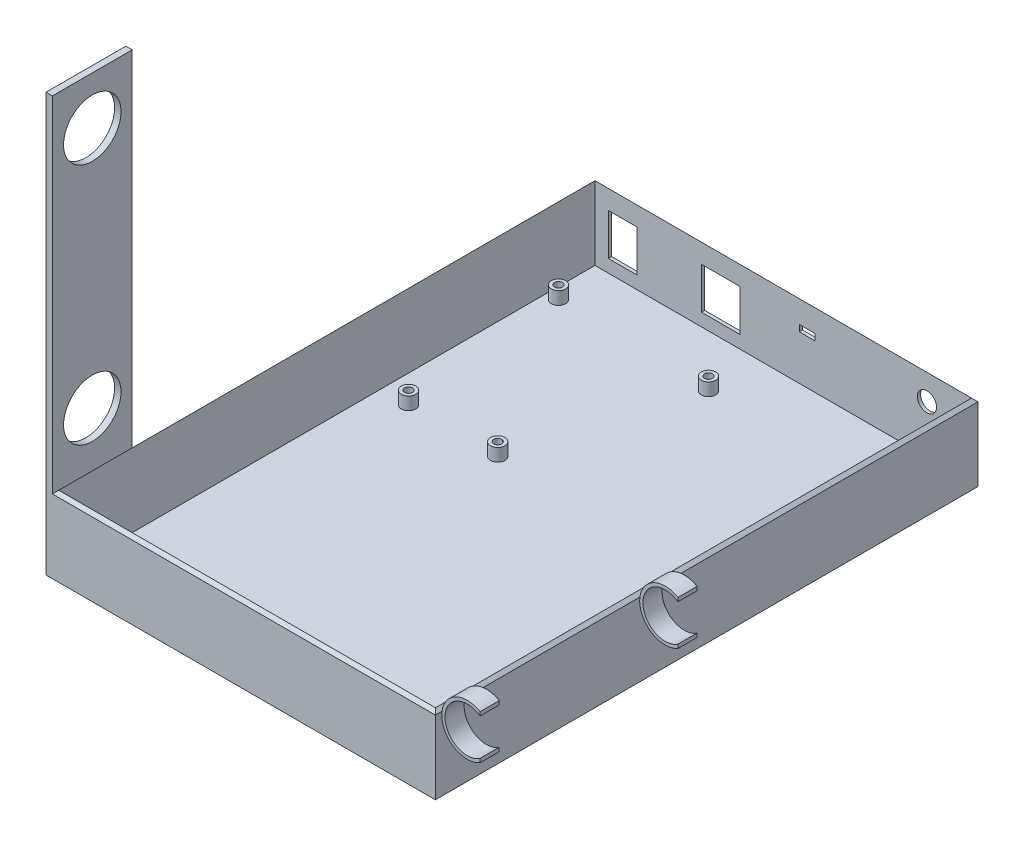
SolidWorks part; units mm, degrees
ref_plane "Front Plane" through (0, 0, 0) normal (0, 0, 1) x (1, 0, 0)
ref_plane "Top Plane" through (0, 0, 0) normal (0, 1, 0) x (1, 0, 0)
ref_plane "Right Plane" through (0, 0, 0) normal (1, 0, 0) x (0, 0, -1)
sketch "Sketch2" plane through (0, 0, 0) normal (0, 1, 0) x (1, 0, 0)
  line L1 (0, 0) -> (120, 0)
  line L2 (0, 0) -> (0, 170)
  line L3 (0, 170) -> (120, 170)
  line L4 (120, 0) -> (120, 170)
  dimension "D1" = 120
  dimension "D2" = 170
extrude "Base Shape" add sketch "Sketch2" along normal blind 25
shell "Shell1" thickness 1
sketch "Sketch3" plane through (0, 25, 0) normal (0, 1, 0) x (1, 0, 0)
  line L1 (0, 0) -> (120, 0)
  line L2 (0, 0) -> (0, 170)
  line L3 (0, 170) -> (120, 170)
  line L4 (120, 0) -> (120, 170)
extrude "Lid Removal" cut sketch "Sketch3" against normal blind 1
sketch "Sketch4" plane through (0, 1, 0) normal (0, 1, 0) x (1, 0, 0)
  line L0 (1, 169) -> (1, 1) construction
  line L1 (119, 169) -> (1, 169) construction
  circle A0 centre (4.54, 154.03) radius 2.25
  circle A1 centre (4.54, 154.03) radius 1.25
  circle A2 centre (9.62, 101.96) radius 2.25
  circle A3 centre (9.62, 101.96) radius 1.25
  circle A4 centre (52.8, 152.76) radius 2.25
  circle A5 centre (52.8, 152.76) radius 1.25
  circle A6 centre (37.56, 101.96) radius 2.25
  circle A7 centre (37.56, 101.96) radius 1.25
  point P4 (2, 168)
  dimension "D1" = 2.5
  dimension "D2" = 4.5
  dimension "D5" = 2.5
  dimension "D6" = 4.5
  dimension "D7" = 2.5
  dimension "D8" = 4.5
  dimension "D9" = 2.5
  dimension "D10" = 4.5
  dimension "D3" = 1
  dimension "D4" = 1
  dimension "D11" = 13.97
  dimension "D12" = 2.54
  dimension "D13" = 15.24
  dimension "D14" = 50.8
  dimension "D15" = 66.04
  dimension "D16" = 7.62
  dimension "D17" = 35.56
extrude "Standoffs" add sketch "Sketch4" along normal blind 4
sketch "Sketch6" plane through (0, 0, -170) normal (0, 0, -1) x (-1, 0, 0)
  line L0 (0, 24) -> (0, 0) construction
  line L1 (-14.175, 18) -> (-5.175, 18)
  line L2 (-14.175, 18) -> (-14.175, 5)
  line L3 (-14.175, 5) -> (-5.175, 5)
  line L4 (-5.175, 18) -> (-5.175, 5)
  line L5 (-46.385, 18) -> (-34.385, 18)
  line L6 (-46.385, 18) -> (-46.385, 5)
  line L7 (-46.385, 5) -> (-34.385, 5)
  line L8 (-34.385, 18) -> (-34.385, 5)
  line L9 (-120, 0) -> (0, 0) construction
  line L10 (-120, 24) -> (-120, 0) construction
  line L11 (-70, 17) -> (-65, 17)
  line L12 (-70, 17) -> (-70, 15)
  line L13 (-70, 15) -> (-65, 15)
  line L14 (-65, 17) -> (-65, 15)
  circle A0 centre (-105, 16) radius 3
  point P8 (-2, 5)
  dimension "D13" = 6
  dimension "D1" = 2
  dimension "D2" = 5
  dimension "D3" = 9
  dimension "D4" = 12
  dimension "D5" = 3.175
  dimension "D6" = 32.385
  dimension "D7" = 13
  dimension "D8" = 13
  dimension "D9" = 5
  dimension "D10" = 2
  dimension "D11" = 15
  dimension "D12" = 50
  dimension "D14" = 16
  dimension "D15" = 15
extrude "Port/Cable Cutouts" cut sketch "Sketch6" against normal up to next
sketch "Sketch7" plane through (0, 0, -170) normal (0, 0, -1) x (-1, 0, 0)
  line L0 (-120, 0) -> (0, 0) construction
  line L1 (-120, 24) -> (-120, 0) construction
  text T0 "SOLENOID      COMP. TESTER"
  dimension "D1" = 7
  dimension "D2" = 5
extrude "Debossed Text" cut sketch "Sketch7" against normal blind 0.2
chamfer "Chamfer1" distance 1 angle 45 4 edges at (0, 24, -85) (60, 24, -170) (120, 24, -85) (60, 24, 0)
sketch "Sketch8" plane through (0, 0, 0) normal (-1, 0, 0) x (0, 0, 1)
  line L1 (0, 0) -> (-25, 0)
  line L2 (0, 0) -> (0, 131)
  line L3 (0, 131) -> (-25, 131)
  line L4 (-25, 0) -> (-25, 131)
  circle A0 centre (-12.5, 116) radius 9
  circle A1 centre (-12.5, 40) radius 9
  point P9 (0, 0)
  dimension "D2" = 18
  dimension "D3" = 18
  dimension "D1" = 25
  dimension "D4" = 76
  dimension "D5" = 40
  dimension "D6" = 12.5
  dimension "D7" = 15
extrude "Flowmeter Mount" add sketch "Sketch8" along normal blind 2
sketch "Sketch9" plane through (0, 0, 0) normal (0, 0, 1) x (1, 0, 0)
  line L0 (120, 23) -> (120, 0) construction
  line L1 (-2, 0) -> (120, 0) construction
  line L2 (132, 28.9282) -> (132, 27.7446)
  line L3 (132, 32.2204) -> (132, 28.9282) construction
  line L4 (132, 15.0718) -> (132, 9.4892) construction
  line L5 (132, 27.7446) -> (132, 16.2554) construction
  line L6 (132, 16.2554) -> (132, 15.0718)
  arc A0 (132, 27.7446) -> (132, 16.2554) centre (128, 22) ccw
  arc A1 (132, 28.9282) -> (132, 15.0718) centre (128, 22) ccw
  arc A2 (132, 15.0718) -> (132, 28.9282) centre (128, 22) ccw construction
  arc A3 (132, 16.2554) -> (132, 27.7446) centre (128, 22) ccw construction
  dimension "D1" = 1
  dimension "D2" = 14
  dimension "D3" = 8
  dimension "D4" = 22
  dimension "D5" = 4
extrude "Boss-Extrude4" add sketch "Sketch9" against normal blind 70 separate body
sketch "Sketch10" plane through (0, 0, 0) normal (0, -1, 0) x (1, 0, 0)
  line L0 (132, -70) -> (132, 0) construction
  line L1 (120, 0) -> (132, 0)
  line L2 (120, 0) -> (120, -2)
  line L3 (120, -2) -> (132, -2)
  line L4 (132, 0) -> (132, -2)
  line L5 (120, 0) -> (120, -170) construction
  line L6 (120, -8) -> (132, -8)
  line L7 (120, -8) -> (120, -64)
  line L8 (120, -64) -> (132, -64)
  line L9 (132, -8) -> (132, -64)
  dimension "D1" = 2
  dimension "D2" = 56
  dimension "D3" = 6
extrude "Cut-Extrude1" cut sketch "Sketch10" against normal through all
